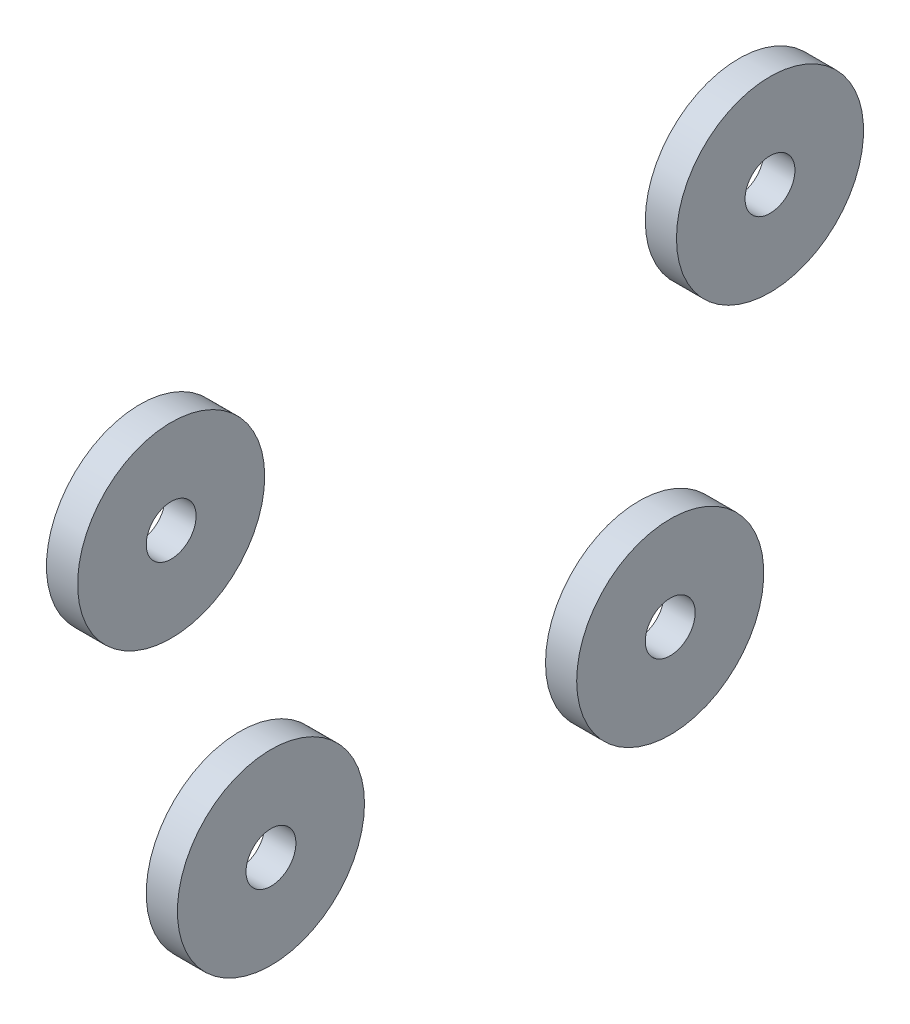
SolidWorks part; units mm, degrees
ref_plane "Front Plane" through (0, 0, 0) normal (0, 0, 1) x (1, 0, 0)
ref_plane "Top Plane" through (0, 0, 0) normal (0, 1, 0) x (1, 0, 0)
ref_plane "Right Plane" through (0, 0, 0) normal (1, 0, 0) x (0, 0, -1)
body saved out of another part "Stock-Fuselage-1" rebuild error yes
shell "Shell1" thickness 6.35 rebuild error yes
sketch "Sketch1" plane through (0, 0, 0) normal (-1, 0, 0) x (0, 0, 1)
  line L0 (0, -77.2285) -> (0, 77.2285) construction
  circle A0 centre (0, 0) radius 25.4
  circle A1 centre (-44.45, 0) radius 9.4615
  circle A2 centre (44.45, 0) radius 9.4615
  dimension "D1" = 44.45
sketch "Sketch2" plane through (19.05, 0, 0) normal (-1, 0, 0) x (0, 0, 1)
  line L0 (0, -57.15) -> (0, -82.55) construction
  circle A0 centre (0, -69.85) radius 9.4615
  spline S0 degree 3 poles (0, -82.55) (0.0356, -82.55) (0.1065, -82.5497) (0.2125, -82.5484) (0.3185, -82.5462) (0.4244, -82.5431) (0.5306, -82.5391) (0.6372, -82.5342) (0.7444, -82.5283) (0.8165, -82.5238) (1.3736, -82.4863) (2.413, -82.3517) (3.9383, -81.9581) (5.4036, -81.379) (6.324, -80.8759) (7.2083, -80.3192) (8.0575, -79.708) (9.2087, -78.6428) (10.2193, -77.4441) (11.0753, -76.1309) (11.763, -74.722) (12.2731, -73.2391) (12.5964, -71.7037) (12.6849, -70.6606) (12.7327, -68.5551) (12.2059, -65.3727) (9.72, -61.2159) (5.8861, -58.2579) (2.7903, -57.3597) (1.1636, -57.2033) (1.0603, -57.194) (0.9072, -57.1821) (0.7552, -57.1722) (0.6041, -57.1641) (0.4534, -57.1578) (0.3028, -57.1533) (0.1518, -57.1506) (0.0507, -57.15) (-0.0507, -57.15) (-0.1518, -57.1506) (-0.3028, -57.1533) (-0.4534, -57.1578) (-0.6041, -57.1641) (-0.7552, -57.1722) (-0.9072, -57.1821) (-1.0603, -57.194) (-1.1636, -57.2033) (-2.7903, -57.3597) (-5.8861, -58.2579) (-9.72, -61.2159) (-12.2059, -65.3726) (-12.7326, -68.555) (-12.6849, -70.6605) (-12.5964, -71.7036) (-12.2731, -73.239) (-11.763, -74.722) (-11.0753, -76.1309) (-10.2193, -77.4441) (-9.3771, -78.443) (-8.6331, -79.1754) (-7.8452, -79.8608) (-7.2083, -80.3192) (-6.324, -80.8759) (-5.4036, -81.379) (-3.9382, -81.9581) (-2.413, -82.3517) (-1.3736, -82.4863) (-0.8165, -82.5238) (-0.7444, -82.5283) (-0.6372, -82.5342) (-0.5306, -82.5391) (-0.4244, -82.5431) (-0.3185, -82.5462) (-0.2125, -82.5484) (-0.1065, -82.5497) (-0.0356, -82.55) (0, -82.55) (0.0356, -82.55) (0.1065, -82.5497) knots -0.001365 0 0 0 0.001365 0.00273 0.004095 0.00546 0.006825 0.00819 0.009555 0.01092 0.01092 0.030557 0.050194 0.069831 0.089468 0.089468 0.109094 0.128721 0.148347 0.167974 0.1876 0.207226 0.226853 0.246479 0.246479 0.305935 0.365391 0.424847 0.484303 0.484303 0.486266 0.488228 0.49019 0.492152 0.494114 0.496076 0.498038 0.5 0.5 0.501962 0.503924 0.505886 0.507848 0.50981 0.511772 0.513734 0.515696 0.515696 0.575152 0.634608 0.694063 0.753519 0.753519 0.773146 0.792773 0.812399 0.832026 0.851653 0.871279 0.881093 0.890906 0.910533 0.910533 0.93017 0.949807 0.969444 0.989081 0.989081 0.990446 0.99181 0.993175 0.99454 0.995905 0.99727 0.998635 1 1 1 1.001365 1.00273 1.004095 only from (0, -82.55) to (0, -82.55) construction
extrude "Cut-Extrude1" cut sketch "Sketch1" against normal blind 53.34 rebuild error yes
extrude "Cut-Extrude2" cut sketch "Sketch2" against normal blind 167.132 contours A0 rebuild error yes
fillet "Fillet1" [suppressed] radius 1.27
fillet "Fillet2" [suppressed] radius 1.27
fillet "Fillet3" radius 1.27 rebuild error yes
fillet "Fillet4" radius 5.08 rebuild error yes
fillet "Fillet5" rebuild error yes type full round
sketch "Sketch3" plane through (152.4, 0, 0) normal (1, 0, 0) x (0, 0, -1)
  line L0 (0, 54.3674) -> (0, -85.873) construction
  line L1 (-86.3722, 54.3674) -> (86.3722, 54.3674) construction
  line L2 (-86.3722, 54.3674) -> (-86.3722, -85.873) construction
  line L3 (-86.3722, -85.873) -> (86.3722, -85.873) construction
  line L4 (86.3722, 54.3674) -> (86.3722, -85.873) construction
  circle A0 centre (-60.9722, 22.6174) radius 5.08
  circle A1 centre (-40.6522, -45.233) radius 5.08
  circle A2 centre (40.6522, -45.233) radius 5.08
  circle A3 centre (60.9722, 22.6174) radius 5.08
  circle A4 centre (-60.9722, 22.6174) radius 19.05
  circle A5 centre (-40.6522, -45.233) radius 19.05
  circle A6 centre (40.6522, -45.233) radius 19.05
  circle A7 centre (60.9722, 22.6174) radius 19.05
  spline S2 degree 4 poles (0, -85.873) (-74.0221, -85.873) (-96.8514, 13.6411) (-119.4286, 54.3674) (0, 54.3674) knots 0 0 0 0 0 1 1 1 1 1 construction
  dimension "D1" = 25.4
  dimension "D5" = 10.16
  dimension "D6" = 38.1
  dimension "D2" = 31.75
  dimension "D3" = 40.64
  dimension "D4" = 45.72
extrude "Boss-Extrude1" add sketch "Sketch3" against normal blind 6.35
fillet "Fillet6" radius 12.7 rebuild error yes
